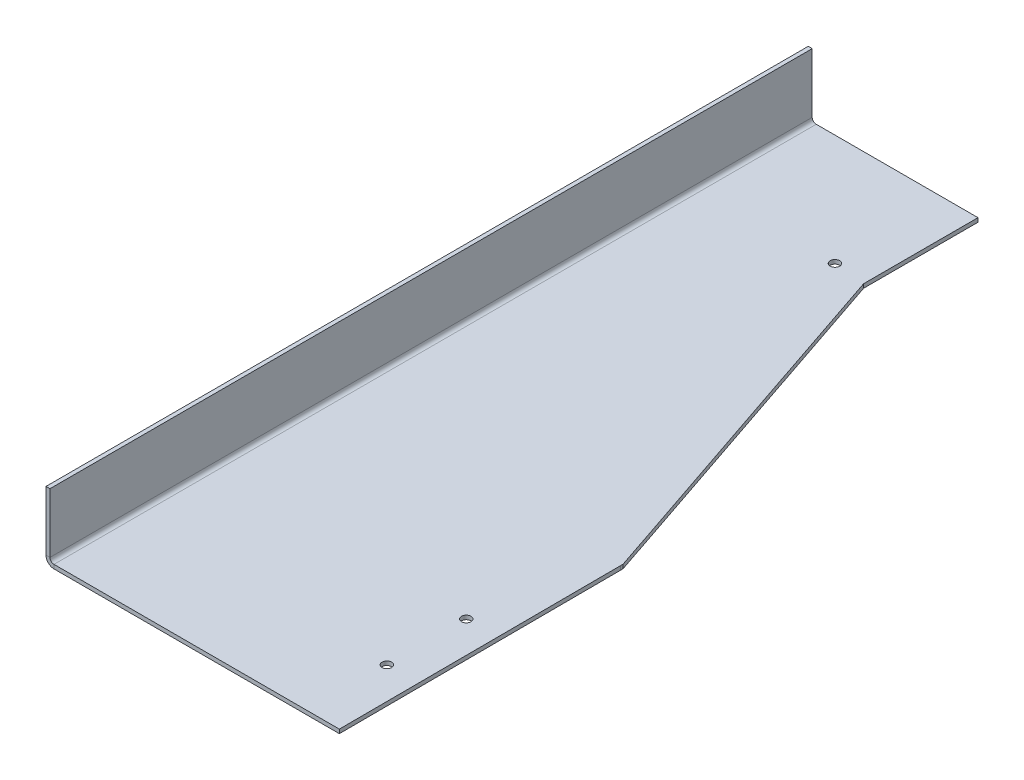
SolidWorks part; units mm, degrees
note: The reader was unsure of these and kept them because the rebuilt part matched: flange length of "Edge-Flange1".
material "6061 Alloy"
ref_plane "Front Plane" through (0, 0, 0) normal (0, 0, 1) x (1, 0, 0)
ref_plane "Top Plane" through (0, 0, 0) normal (0, 1, 0) x (1, 0, 0)
ref_plane "Right Plane" through (0, 0, 0) normal (1, 0, 0) x (0, 0, -1)
sketch "Sketch1" plane through (0, 0, 0) normal (0, 1, 0) x (1, 0, 0)
  line L0 (0, 304.8) -> (76.2, 304.8)
  line L1 (76.2, 304.8) -> (152.4, 0)
  line L2 (152.4, 0) -> (0, 0)
  line L3 (0, 0) -> (0, 304.8)
  dimension "D1" = 76.2
  dimension "D2" = 304.8
  dimension "D3" = 152.4
base flange "Base-Flange1" sketch "Sketch1" thickness 1.5875 reverse thickness direction no parameters "D1"=254
edge flange "Edge-Flange1" sketch "Sketch8" flange angle 90 flange length 25.4 flange position material inside bend radius 1.6002 thickness 1.5875 relief rectangular parameters "D6"=10
sketch "Sketch8" plane through (0, 0, 0) normal (-1, 0, 0) x (0, 0, 1)
  line L2 (-304.8, 0) -> (-304.8, 25.4)
  line L3 (-304.8, 25.4) -> (0, 25.4)
  line L4 (0, 25.4) -> (0, 0)
  line L13 (-304.8, 0) -> (0, 0) construction
  line L14 (-304.8, 0) -> (0, 0)
bend "EdgeBend1" bend radius 1.6002 bend angle 90 parameters "D5"=1
sketch "Sketch10" plane through (0, 0, 0) normal (0, 1, 0) x (1, 0, 0)
  line L0 (67.8768, 304.8) -> (67.8768, 261.2174)
  line L1 (76.2, 304.8) -> (3.1877, 304.8) construction
  line L2 (67.8768, 261.2174) -> (67.8768, 259.0657)
  line L3 (67.8768, 259.0657) -> (116.9144, 113.8499)
  line L4 (116.9144, 113.8499) -> (116.9144, 112.8482)
  line L5 (116.9144, 112.8482) -> (117.3069, 0)
  line L6 (3.1877, 0) -> (152.4, 0) construction
extrude "Cut-Extrude1" cut sketch "Sketch10" against normal through all and the other way through all normal cut yes
hole_wizard "#6 Clearance Hole1" positions "Sketch12" profile "Sketch11" hole size "#6" standard "ANSI Inch" end condition through all
sketch "Sketch12" plane through (0, -1.5875, 0) normal (0, -1, 0) x (-1, 0, 0)
  point P0 (-55.118, 260.35)
  point P4 (-104.5432, 31.75)
  point P7 (-104.5432, 63.5)
sketch "Sketch11" plane through (55.118, -1.5875, -260.35) normal (1, 0, 0) x (0, 0, -1)
  line L0 (0, 0) -> (0, 26.9875)
  line L1 (0, 26.9875) -> (1.8986, 26.9875)
  line L2 (1.8986, 26.9875) -> (1.8986, 0)
  line L5 (1.8986, 0) -> (0, 0)
  line L11 (0, -6.35) -> (0, 107.95) construction
  dimension "Thru Hole Dia." = 3.7973
  dimension "Thru Hole Depth" = 26.9875
sketch "Bend-Lines1" [suppressed] plane through (0, 0, 0) normal (0, 1, 0) x (1, 0, 0)
sketch "Bounding-Box1" [suppressed] plane through (0, 0, 0) normal (0, 1, 0) x (1, 0, 0)
sheet metal parameters "Sheet-Metal1" thickness 1.5875 parameters "D1"=254
flat pattern "Flat-Pattern1" [suppressed]
sketch "Bend-Lines2" plane through (0, 0, 0) normal (0, 1, 0) x (1, 0, 0)
sketch3d "Bounding-Box2" [suppressed]
  line L0 (0, 0, 0) -> (0, 304.8, 0) construction
  line L1 (-152.4, 0, 0) -> (-152.4, 304.8, 0) construction
  line L2 (0, 0, 0) -> (-152.4, 0, 0) construction
  line L3 (0, 304.8, 0) -> (-152.4, 304.8, 0) construction
sheet metal parameters "Sheet-Metal2" thickness 1.5875 parameters "D1"=254
flat pattern "Flat-Pattern1"
sketch "Bend-Lines2" plane through (0, 0, 0) normal (0, 1, 0) x (1, 0, 0)
  line L0 (1.3075, 304.8) -> (1.3075, 0) construction
  line L1 (1.3075, 304.8) -> (1.3075, 0) construction
sketch3d "Bounding-Box2" [suppressed]
  line L0 (-24.3725, 0, 0) -> (-24.3725, 304.8, 0) construction
  line L1 (152.4, 0, 0) -> (152.4, 304.8, 0) construction
  line L2 (-24.3725, 0, 0) -> (152.4, 0, 0) construction
  line L3 (-24.3725, 304.8, 0) -> (152.4, 304.8, 0) construction
bend of the flat pattern "Flatten-<EdgeBend1>1"
sheet metal parameters "Sheet-Metal3" thickness 1.5875 parameters "D1"=254
flat pattern "Flat-Pattern1"
sketch "Bend-Lines2" plane through (0, 0, 0) normal (0, 1, 0) x (1, 0, 0)
  line L0 (1.3075, 304.8) -> (1.3075, 0) construction
  line L1 (1.3075, 304.8) -> (1.3075, 0) construction
sketch3d "Bounding-Box2" [suppressed]
  line L0 (117.3069, 0, 0) -> (117.3069, 304.8, 0) construction
  line L1 (-24.3725, 0, 0) -> (-24.3725, 304.8, 0) construction
  line L2 (117.3069, 0, 0) -> (-24.3725, 0, 0) construction
  line L3 (117.3069, 304.8, 0) -> (-24.3725, 304.8, 0) construction
bend of the flat pattern "Flatten-<EdgeBend1>1"
sheet metal parameters "Sheet-Metal4" thickness 1.5875 parameters "D1"=254
flat pattern "Flat-Pattern1"
sketch "Bend-Lines2" plane through (0, 0, 0) normal (0, 1, 0) x (1, 0, 0)
  line L0 (1.3075, 304.8) -> (1.3075, 0) construction
  line L1 (1.3075, 304.8) -> (1.3075, 0) construction
sketch3d "Bounding-Box2" [suppressed]
  line L0 (117.3069, 0, 0) -> (117.3069, 304.8, 0) construction
  line L1 (-24.3725, 0, 0) -> (-24.3725, 304.8, 0) construction
  line L2 (117.3069, 0, 0) -> (-24.3725, 0, 0) construction
  line L3 (117.3069, 304.8, 0) -> (-24.3725, 304.8, 0) construction
bend of the flat pattern "Flatten-<EdgeBend1>1"
